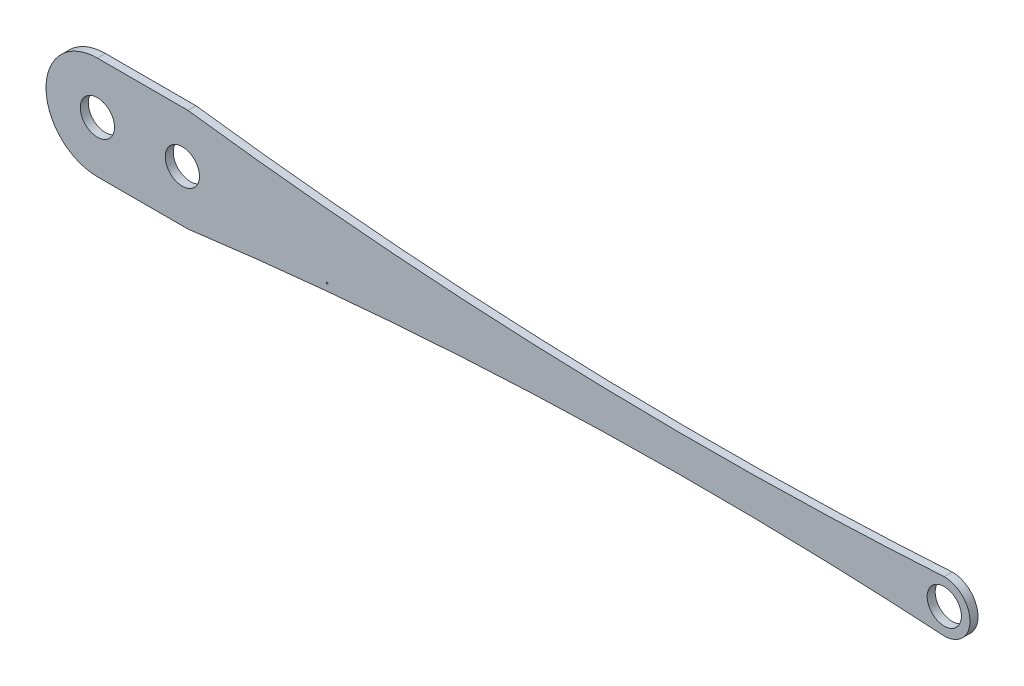
SolidWorks part; units mm, degrees
ref_plane "Front Plane" through (0, 0, 0) normal (0, 0, 1) x (1, 0, 0)
ref_plane "Top Plane" through (0, 0, 0) normal (0, 1, 0) x (1, 0, 0)
ref_plane "Right Plane" through (0, 0, 0) normal (1, 0, 0) x (0, 0, -1)
sketch "Sketch4" plane through (0, 0, 0) normal (0, 0, 1) x (1, 0, 0)
  line L0 (0, 0) -> (418.6413, 0) construction
  line L1 (0, 25.4) -> (44.7423, 25.4)
  line L2 (0, -25.4) -> (44.7423, -25.4)
  arc A0 (0, 25.4) -> (0, -25.4) centre (0, 0) ccw
  circle A2 centre (0, 0) radius 8.4667
  circle A3 centre (42.004, 0) radius 8.4667
  circle A4 centre (418.6413, 0) radius 8.4667
  arc A5 (418.6413, -12.7) -> (418.6413, 12.7) centre (418.6413, 0) ccw
  arc A6 (44.7423, 25.4) -> (51.1817, 24.5702) centre (44.7423, 0) cw
  arc A7 (51.1817, -24.5702) -> (44.7423, -25.4) centre (44.7423, 0) cw
  spline S0 degree 2 poles (44.7423, 25.4) (231.0685, 1.0772) (418.6413, 12.7) knots 0 0 0 1 1 1
  spline S1 degree 2 poles (44.7423, -25.4) (231.0685, -1.0772) (418.6413, -12.7) knots 0 0 0 1 1 1
  point P3 (228.6, 0)
  dimension "D3" = 16.9333
  dimension "D5" = 25.4
  dimension "D1" = 50.8
  dimension "D2" = 418.6413
  dimension "D6" = 15.24
  dimension "D7" = 15.24
  dimension "D8" = 42.004
extrude "Boss-Extrude2" add sketch "Sketch4" along normal blind 3.9688 contours L2 S1 A5 S0 L1 A0 A2 A3 A4 region at (159.1874, 0, 0)
scale "Scale1" scale about centroid uniform scaling yes scale factor 0.75
sketch "Sketch5" plane through (0, 0, 3.4727) normal (0, 0, 1) x (1, 0, 0)
  circle A0 centre (124.9402, -10.6445) radius 0.2857
  dimension "D1" = 0.5715
extrude "Cut-Extrude1" cut sketch "Sketch5" against normal through all both
